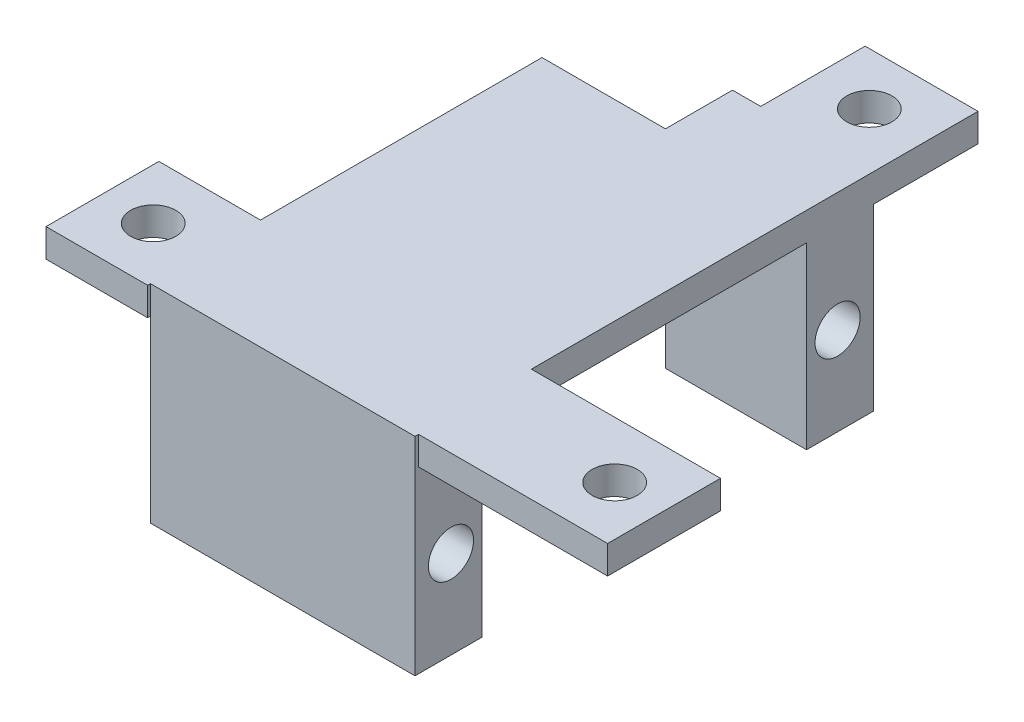
SolidWorks part; units mm, degrees
ref_plane "Front Plane" through (0, 0, 0) normal (0, 0, 1) x (1, 0, 0)
ref_plane "Top Plane" through (0, 0, 0) normal (0, 1, 0) x (1, 0, 0)
ref_plane "Right Plane" through (0, 0, 0) normal (1, 0, 0) x (0, 0, -1)
sketch "Sketch1" plane through (0, 0, 0) normal (0, 1, 0) x (1, 0, 0)
  line L0 (1.1, 16.25) -> (1.1, 11.5)
  line L1 (-17.65, -16.25) -> (17.65, -16.25)
  line L2 (-17.65, -16.25) -> (-17.65, 16.25)
  line L3 (-17.65, 16.25) -> (17.65, 16.25)
  line L4 (17.65, -16.25) -> (17.65, 16.25)
  line L5 (-17.65, -16.25) -> (17.65, 16.25) construction
  line L6 (-17.65, 16.25) -> (17.65, -16.25) construction
  line L7 (1.1, 11.5) -> (-17.65, 11.5)
  line L8 (1.1, -16.25) -> (1.1, -11.5)
  line L9 (1.1, -11.5) -> (-17.65, -11.5)
  line L10 (1.1, 11.5) -> (1.1, -11.5)
  line L11 (-8.9, 16.25) -> (-8.9, 11.5)
  line L12 (1.1, -8) -> (14.5, -8)
  line L13 (14.5, -8) -> (14.5, -16)
  line L14 (14.5, -16) -> (1.1, -16)
  line L15 (-6.9, 16.25) -> (-6.9, 23.65)
  line L16 (-6.9, 23.65) -> (1.1, 23.65)
  line L17 (1.1, 23.65) -> (1.1, 16.25)
  line L18 (-17.65, -16.45) -> (-24.85, -16.45)
  line L19 (-24.85, -16.45) -> (-24.85, -8.45)
  line L20 (-24.85, -8.45) -> (-17.65, -8.45)
  line L21 (-17.65, -16.45) -> (-17.65, -8.45)
  circle A0 centre (11, -12) radius 1.6
  circle A1 centre (-2.9, 19.95) radius 1.6
  circle A2 centre (-21.25, -12.45) radius 1.6
  point P0 (0, 0)
  point P11 (1.1, 0)
  point P36 (14.5, -12)
  point P38 (-21.25, -8.45)
  point P39 (-24.85, -12.45)
  point P41 (1.1, 19.95)
  point P42 (-2.9, 23.65)
  dimension "D6" = 3.2
  dimension "D7" = 3.2
  dimension "D8" = 3.2
  dimension "D1" = 32.5
  dimension "D2" = 23
  dimension "D3" = 8.75
  dimension "D4" = 18.75
  dimension "D5" = 16.55
  dimension "D9" = 11
  dimension "D10" = 12
  dimension "D11" = 8
  dimension "D12" = 12.45
  dimension "D13" = 8
  dimension "D14" = 21.25
  dimension "D15" = 8
  dimension "D16" = 2.9
  dimension "D17" = 19.95
  dimension "D18" = 14.5
extrude "Boss-Extrude1" add sketch "Sketch1" along normal blind 2 contours L18 L21 L2 L20 L19 A2 | A2 | L10 L7 L2 L9 | L8 L9 L2 L1 | L3 L11 L7 L0 | A1 | L17 L16 L15 L3 A1 | A0 | L14 L13 L12 L10 A0 region at (-3.9, 0, -13.875) region at (-2.9, 0, -16.359) region at (-8.275, 0, 0) region at (7.5405, 0, 12) region at (-8.275, 0, 13.875) region at (-17.7576, 0, 9.975) region at (11, 0, 12) region at (-2.9, 0, -19.95) region at (-21.25, 0, 12.45)
extrude "Boss-Extrude2" add sketch "Sketch1<5>" against normal blind 12.7 from surface contours L3 L11 L7 L0 | L8 L9 L2 L1 region at (-3.9, 0, -13.875) region at (-8.275, 0, 13.875) starting at face at (-7.4063, 0, 1.7188)
sketch "Sketch1<5>" plane through (0, 0, 0) normal (0, 1, 0) x (1, 0, 0) same geometry as "Sketch1"
extrude "Cut-Extrude1" cut sketch "Sketch1<6>" against normal through all both and the other way through all contours A1 | A0 | A2 region at (11, 0, 12) region at (-2.9, 0, -19.95) region at (-21.25, 0, 12.45)
sketch "Sketch1<6>" plane through (0, 0, 0) normal (0, 1, 0) x (1, 0, 0) same geometry as "Sketch1"
sketch "Sketch2" plane through (0, 0, 0) normal (1, 0, 0) x (0, 0, -1)
  line L0 (13.7, -6.45) -> (-13.7, -6.45) construction
  circle A0 centre (-13.7, -6.45) radius 1.6
  circle A1 centre (13.7, -6.45) radius 1.6
  point P4 (0, -6.45)
  dimension "D1" = 3.2
  dimension "D2" = 3.2
  dimension "D3" = 27.4
  dimension "D4" = 6.45
extrude "Cut-Extrude2" cut sketch "Sketch2" against normal blind 8 from surface starting at face at (1.1, -3.5667, 14.5833)
